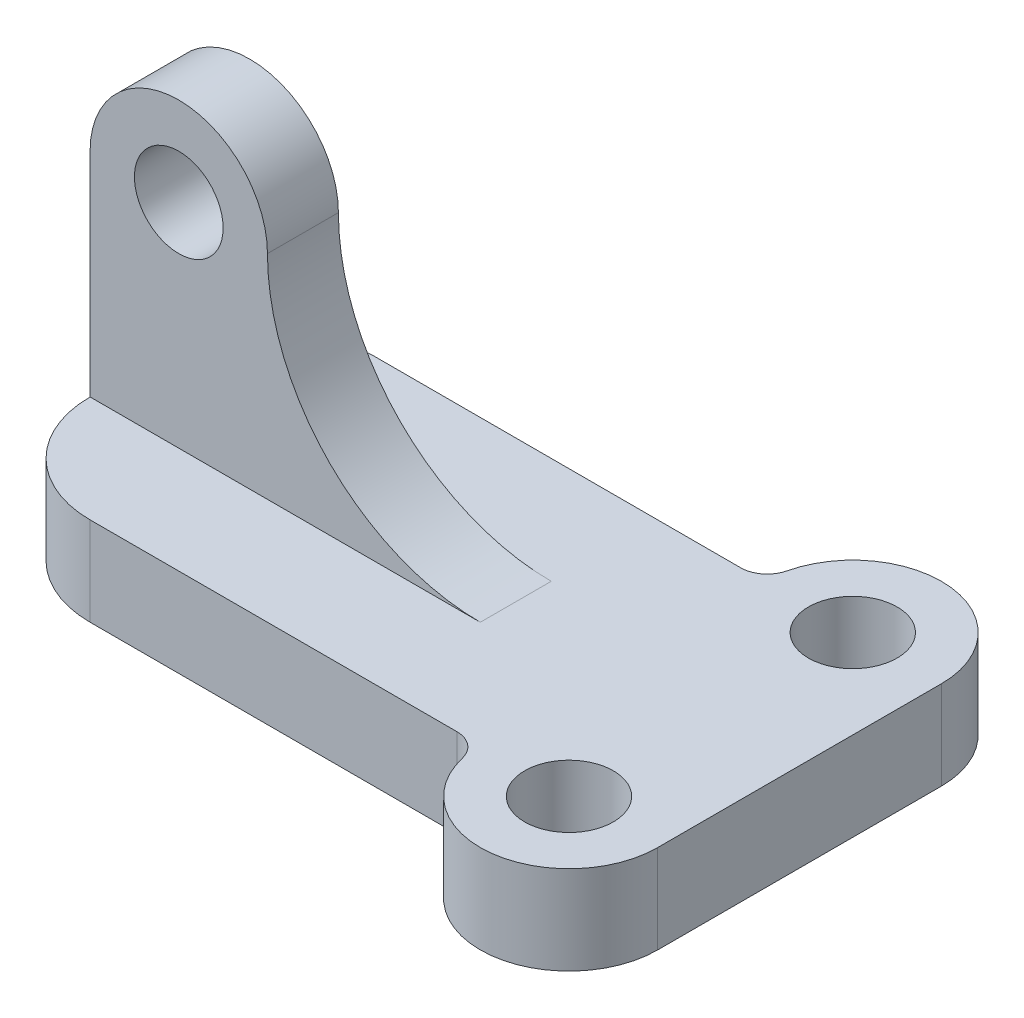
SolidWorks part; units mm, degrees
ref_plane "Front Plane" through (0, 0, 0) normal (0, 0, 1) x (1, 0, 0)
ref_plane "Top Plane" through (0, 0, 0) normal (0, 1, 0) x (1, 0, 0)
ref_plane "Right Plane" through (0, 0, 0) normal (1, 0, 0) x (0, 0, -1)
sketch "Sketch1" plane through (0, 0, 0) normal (0, 1, 0) x (1, 0, 0)
  line L1 (0, 32) -> (61, 32)
  line L2 (0, 32) -> (0, 0)
  line L3 (0, 0) -> (61, 0)
  line L5 (76, 32) -> (76, 0)
  arc A0 (76, 32) -> (56, 32) centre (66, 32) ccw
  circle A1 centre (66, 32) radius 5
  circle A2 centre (66, 0) radius 5
  arc A3 (76, 0) -> (56, 0) centre (66, 0) cw
  dimension "D3" = 20
  dimension "D4" = 10
  dimension "D1" = 32
  dimension "D2" = 66
extrude "Boss-Extrude1" add sketch "Sketch1" along normal blind 10
fillet "Fillet1" radius 3 1 edges at (56, 5, 0)
fillet "Fillet2" radius 3 1 edges at (56, 5, -32)
fillet "Fillet3" radius 12 1 edges at (0, 5, -32)
fillet "Fillet4" radius 12 1 edges at (0, 5, 0)
ref_plane "Plane1" through (0, 0, -16) normal (0, 0, 1) x (1, 0, 0)
sketch "Sketch2" plane through (0, 0, -16) normal (0, 0, 1) x (1, 0, 0)
  line L0 (0, 10) -> (0, 34)
  line L1 (20, 10) -> (20, 34)
  line L2 (0, 10) -> (20, 10)
  arc A0 (0, 34) -> (20, 34) centre (10, 34) cw
  circle A1 centre (10, 34) radius 5
  dimension "D2" = 10
  dimension "D1" = 20
extrude "Boss-Extrude2" add sketch "Sketch2" along normal mid plane 8
fillet "Fillet5" radius 24 3 edges at (20, 22, -12) (20, 22, -20) (20, 10, -16)
